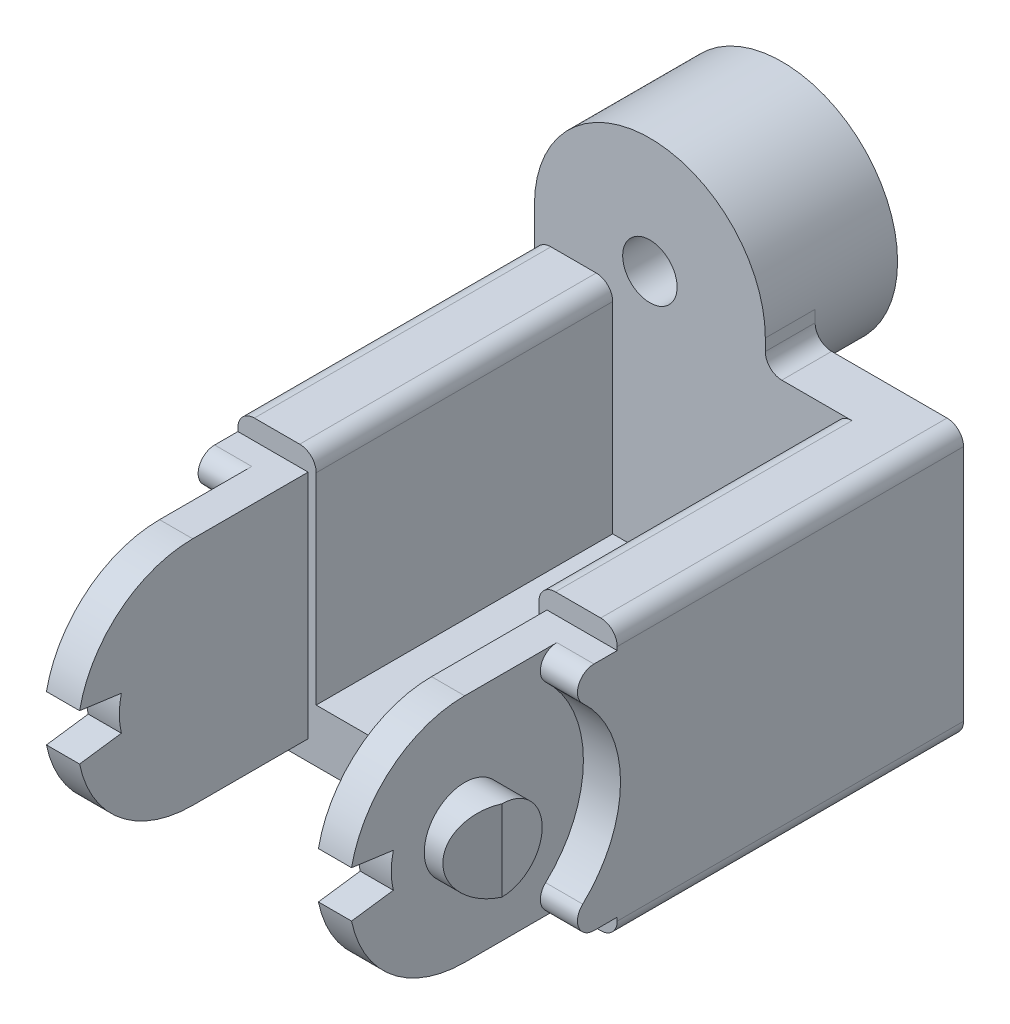
SolidWorks part; units mm, degrees
ref_plane "Front Plane" through (0, 0, 0) normal (0, 0, 1) x (1, 0, 0)
ref_plane "Top Plane" through (0, 0, 0) normal (0, 1, 0) x (1, 0, 0)
ref_plane "Right Plane" through (0, 0, 0) normal (1, 0, 0) x (0, 0, -1)
sketch "Sketch1" plane through (0, 0, 0) normal (0, 0, 1) x (1, 0, 0)
  line L0 (8, -1.7119) -> (15, -1.7119)
  line L2 (15, -18.1319) -> (-6, -18.1319)
  line L6 (-7, -17.1319) -> (-7, 0)
  line L8 (7, 0) -> (7, -0.7119)
  line L15 (16, -2.7119) -> (16, -17.1319)
  circle A3 centre (0, 0) radius 1.65
  arc A4 (15, -18.1319) -> (16, -17.1319) centre (15, -17.1319) ccw
  arc A5 (15, -1.7119) -> (16, -2.7119) centre (15, -2.7119) cw
  arc A7 (-6, -18.1319) -> (-7, -17.1319) centre (-6, -17.1319) cw
  arc A13 (7, -0.7119) -> (8, -1.7119) centre (8, -0.7119) ccw
  arc A14 (7, 0) -> (-7, 0) centre (0, 0) ccw
extrude "Boss-Extrude1" add sketch "Sketch1" along normal blind 40
sketch "Sketch2" plane through (0, 0, 40) normal (0, 0, 1) x (1, 0, 0)
  line L3 (-2.2532, -14.9119) -> (-2.2532, -2.7119)
  line L5 (-2.2532, -14.9119) -> (11.2532, -14.9119)
  line L6 (11.2532, -14.9119) -> (11.2532, -2.7119)
  line L7 (-3.2532, -1.7119) -> (-6, -1.7119)
  line L9 (12.2532, -1.7119) -> (8, -1.7119)
  line L10 (7, 0) -> (7, -0.7119)
  line L12 (-7, 0) -> (-7, -2.7119)
  arc A3 (11.2532, -2.7119) -> (12.2532, -1.7119) centre (12.2532, -2.7119) cw
  arc A4 (-2.2532, -2.7119) -> (-3.2532, -1.7119) centre (-3.2532, -2.7119) ccw
  arc A7 (7, -0.7119) -> (8, -1.7119) centre (8, -0.7119) ccw
  arc A8 (-6, -1.7119) -> (-7, -2.7119) centre (-6, -2.7119) ccw
  arc A9 (7, 0) -> (-7, 0) centre (0, 0) ccw
extrude "Cut-Extrude1" cut sketch "Sketch2" against normal offset from surface (31.98 mm away) 8.02 up to face at (6.4, -7.079, 0)
sketch "Sketch3" plane through (0, 0, 0) normal (0, 0, -1) x (-1, 0, 0)
  line L1 (-7, 0) -> (-7, -0.7119)
  line L4 (-16, -2.7119) -> (-16, -17.1319)
  line L5 (7, 0) -> (7, -17.1319)
  line L6 (-15, -18.1319) -> (6, -18.1319)
  line L7 (-15, -1.7119) -> (-8, -1.7119)
  arc A4 (-15, -1.7119) -> (-16, -2.7119) centre (-15, -2.7119) ccw
  arc A5 (-16, -17.1319) -> (-15, -18.1319) centre (-15, -17.1319) ccw
  arc A6 (6, -18.1319) -> (7, -17.1319) centre (6, -17.1319) ccw
  circle A7 centre (0, 0) radius 3.6
  arc A9 (-8, -1.7119) -> (-7, -0.7119) centre (-8, -0.7119) ccw
  arc A12 (-7, 0) -> (7, 0) centre (0, 0) ccw
extrude "Cut-Extrude2" cut sketch "Sketch3" against normal blind 5
sketch "Sketch4" plane through (0, 0, 40) normal (0, 0, 1) x (1, 0, 0)
  line L1 (-2.74, -16.9219) -> (-2.74, -2.9219)
  line L3 (11.74, -16.9219) -> (11.74, -2.9219)
  line L5 (-7, -1.7119) -> (16, -1.7119)
  line L6 (-7, -1.7119) -> (-7, -2.9219)
  line L7 (-7, -2.9219) -> (-2.74, -2.9219)
  line L8 (16, -1.7119) -> (16, -2.9219)
  line L9 (11.74, -2.9219) -> (16, -2.9219)
  line L10 (-7, -18.1319) -> (16, -18.1319)
  line L11 (-7, -18.1319) -> (-7, -16.9219)
  line L12 (-7, -16.9219) -> (-2.74, -16.9219)
  line L13 (16, -18.1319) -> (16, -16.9219)
  line L14 (11.74, -16.9219) -> (16, -16.9219)
extrude "Cut-Extrude3" cut sketch "Sketch4" against normal blind 14
sketch "Sketch5" plane through (16, 0, 0) normal (1, 0, 0) x (0, 0, -1)
  line L0 (-39.8586, -8.5219) -> (-37.3243, -8.8719)
  line L1 (-39.8586, -11.3219) -> (-37.3243, -10.9719)
  line L2 (-33, -2.9219) -> (-40, -2.9219)
  line L3 (-40, -2.9219) -> (-40, -16.9219)
  line L4 (-40, -16.9219) -> (-33, -16.9219)
  arc A0 (-39.8586, -11.3219) -> (-33, -16.9219) centre (-33, -9.9219) ccw
  arc A1 (-37.3243, -8.8719) -> (-37.3243, -10.9719) centre (-33, -9.9219) ccw
  arc A2 (-33, -2.9219) -> (-39.8586, -8.5219) centre (-33, -9.9219) ccw
extrude "Cut-Extrude4" cut sketch "Sketch5" against normal up to surface (23 mm away) up to face at (-7, -7.9375, 21.004)
sketch "Sketch6" plane through (16, 0, 0) normal (1, 0, 0) x (0, 0, -1)
  line L0 (-27.4107, -2.9219) -> (-31.3148, -2.9219)
  line L1 (-27.4107, -16.9219) -> (-31.3148, -16.9219)
  circle A0 centre (-33, -9.9219) radius 2.45
  arc A1 (-27.4107, -16.9219) -> (-28.0923, -15.1902) centre (-27.4107, -15.9219) cw
  arc A2 (-27.4107, -2.9219) -> (-28.0923, -4.6536) centre (-27.4107, -3.9219) ccw
  arc A3 (-31.3148, -2.9219) -> (-31.3148, -16.9219) centre (-33, -9.9219) ccw
  arc A4 (-28.0923, -15.1902) -> (-28.0923, -4.6536) centre (-33, -9.9219) ccw
extrude "Cut-Extrude5" cut sketch "Sketch6" against normal blind 2.25
extrude "Cut-Extrude6" cut sketch "Sketch6<2>" along normal blind 2.25 from surface starting at face at (-7, -8.5045, 25.1805)
sketch "Sketch6<2>" plane through (16, 0, 0) normal (1, 0, 0) x (0, 0, -1) same geometry as "Sketch6"
sketch "Sketch7" plane through (0, -2.9219, 0) normal (0, 1, 0) x (1, 0, 0)
  line L0 (-7, -33) -> (-5.875, -35.45)
  line L1 (-5.875, -35.45) -> (-7, -35.45)
  line L2 (-7, -35.45) -> (-7, -33)
  line L3 (16, -33) -> (16, -35.45)
  line L4 (16, -35.45) -> (14.875, -35.45)
  line L5 (14.875, -35.45) -> (16, -33)
extrude "Cut-Extrude7" cut sketch "Sketch7" against normal up to surface (14 mm away) up to face at (13.83, -16.9219, 28.8036)
sketch "Sketch8" plane through (0, 0, 5) normal (0, 0, -1) x (-1, 0, 0)
  line L0 (-2, -18.1319) -> (7, -18.1319)
  line L2 (7, -18.1319) -> (7, -15.1319)
  line L3 (7, -15.1319) -> (-1, -15.1319)
  line L4 (-1, -17.1319) -> (-1, -15.1319)
  arc A1 (-2, -18.1319) -> (-1, -17.1319) centre (-2, -17.1319) ccw
extrude "Cut-Extrude8" cut sketch "Sketch8" against normal blind 17
